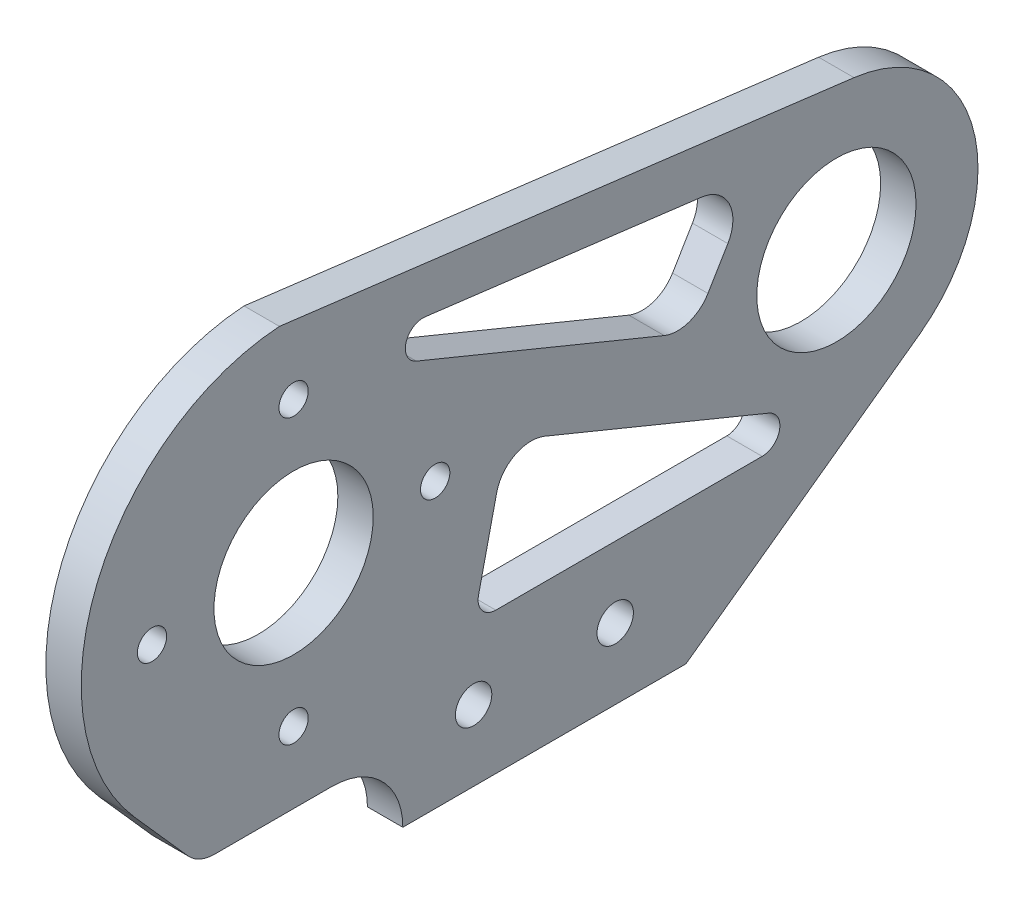
SolidWorks part; units mm, degrees
material "3003 Alloy"
ref_plane "Front Plane" through (0, 0, 0) normal (0, 0, 1) x (1, 0, 0)
ref_plane "Top Plane" through (0, 0, 0) normal (0, 1, 0) x (1, 0, 0)
ref_plane "Right Plane" through (0, 0, 0) normal (1, 0, 0) x (0, 0, -1)
sketch "Sketch1" plane through (0, 0, 0) normal (1, 0, 0) x (0, 0, -1)
  line L0 (25.4, 12.7) -> (38.1, 12.7) construction
  line L1 (0, 0) -> (76.2, 0)
  line L5 (38.1, 12.7) -> (63.5, 12.7) construction
  line L6 (63.5, 12.7) -> (103.1875, 12.7) construction
  line L7 (103.1875, 12.7) -> (103.1875, 50.8) construction
  line L8 (103.1875, 50.8) -> (42.6031, 50.8) construction
  line L9 (76.2, 0) -> (118.0516, 30.2034)
  line L12 (5.8039, 50.8851) -> (5.8039, 76.2851) construction
  line L13 (0, 0) -> (-22.705, 25.6096)
  line L15 (38.1, 12.7) -> (38.1, 39.0177) construction
  line L18 (5.8039, 50.8851) -> (5.8039, 25.4851) construction
  line L19 (5.8039, 50.8851) -> (31.2039, 50.8851) construction
  line L20 (5.8039, 50.8851) -> (-19.5961, 50.8851) construction
  line L21 (106.3406, 76.0035) -> (3.2574, 88.8999)
  line L22 (103.1875, 50.8) -> (5.8039, 50.8851) construction
  circle A0 centre (38.1, 12.7) radius 3.2639
  circle A1 centre (63.5, 12.7) radius 3.2639
  circle A2 centre (103.1875, 50.8) radius 14.2875
  arc A3 (118.0516, 30.2034) -> (106.3406, 76.0035) centre (103.1875, 50.8) ccw
  circle A4 centre (5.8039, 50.8851) radius 14.2875
  circle A5 centre (5.8039, 76.2851) radius 2.6289
  arc A9 (3.2574, 88.8999) -> (-22.705, 25.6096) centre (5.8039, 50.8851) ccw
  circle A10 centre (5.8039, 25.4851) radius 2.6289
  circle A11 centre (31.2039, 50.8851) radius 2.6289
  circle A12 centre (-19.5961, 50.8851) radius 2.6289
  dimension "D5" = 6.5278
  dimension "D6" = 6.5278
  dimension "D9" = 28.575
  dimension "D10" = 50.8
  dimension "D11" = 28.575
  dimension "D13" = 5.2578
  dimension "D15" = 76.2
  dimension "D17" = 5.2578
  dimension "D19" = 5.2578
  dimension "D21" = 5.2578
  dimension "D2" = 76.2
  dimension "D3" = 12.7
  dimension "D4" = 25.4
  dimension "D7" = 39.6875
  dimension "D8" = 38.1
  dimension "D12" = 25.4
  dimension "D16" = 97.3836
  dimension "D14" = 25.4
  dimension "D18" = 25.4
  dimension "D20" = 25.4
  dimension "D22" = 12.7
  dimension "D23" = 12.7
extrude "Boss-Extrude1" add sketch "Sketch1" along normal blind 6.35
sketch "Sketch2" plane through (0, 0, 0) normal (-1, 0, 0) x (0, 0, 1)
  line L1 (0, 0) -> (-25.4, 0)
  line L3 (0, 12.7) -> (-25.4, 12.7)
  line L4 (-25.4, 0) -> (-25.4, 12.7)
  line L5 (0, 12.7) -> (11.9508, 12.7)
  line L7 (0, 0) -> (11.9508, 0)
  line L8 (11.9508, 12.7) -> (11.9508, 0)
  dimension "D1" = 25.4
  dimension "D2" = 12.7
extrude "Cut-Extrude1" cut sketch "Sketch2" against normal blind 6.35
sketch "Sketch3" plane through (0, 0, 0) normal (-1, 0, 0) x (0, 0, 1)
  line L0 (-105.9575, 25.4) -> (-43.9039, 50.8851)
  line L1 (-43.9039, 50.8851) -> (-38.1, 25.4)
  line L2 (-38.1, 25.4) -> (-105.9575, 25.4)
  line L3 (-88.7135, 69.8894) -> (-77.3334, 50.8851)
  line L4 (-77.3334, 50.8851) -> (-5.8039, 80.262)
  line L5 (-5.8039, 80.262) -> (-88.7135, 69.8894)
  line L6 (-25.4, 0) -> (-76.2, 0) construction
  line L7 (-77.3334, 50.8851) -> (-43.9039, 50.8851) construction
  line L9 (-31.2039, 50.8851) -> (-43.9039, 50.8851) construction
  line L10 (-5.8039, 76.2851) -> (-5.8039, 80.262) construction
  line L11 (-106.3406, 76.0035) -> (-3.2574, 88.8999) construction
  circle A0 centre (-103.1875, 50.8) radius 14.2875 construction
  dimension "D4" = 22.225
  dimension "D1" = 25.4
  dimension "D2" = 12.7
  dimension "D3" = 12.7
  dimension "D5" = 12.7
  dimension "D6" = 8.255
extrude "Cut-Extrude2" cut sketch "Sketch3" against normal through all
fillet "Fillet1" radius 6.35 1 edges at (3.175, 50.8851, -77.3334)
fillet "Fillet2" radius 6.35 1 edges at (3.175, 69.8894, -88.7135)
fillet "Fillet3" radius 3.175 1 edges at (3.175, 80.262, -5.8039)
fillet "Fillet4" radius 6.35 1 edges at (3.175, 50.8851, -43.9039)
fillet "Fillet5" radius 3.175 1 edges at (3.175, 25.4, -38.1)
fillet "Fillet6" radius 3.175 1 edges at (3.175, 25.4, -105.9575)
fillet "Fillet7" radius 12.7 1 edges at (3.175, 12.7, -25.4)
fillet "Fillet8" radius 6.35 1 edges at (3.175, 12.7, 11.2596)
